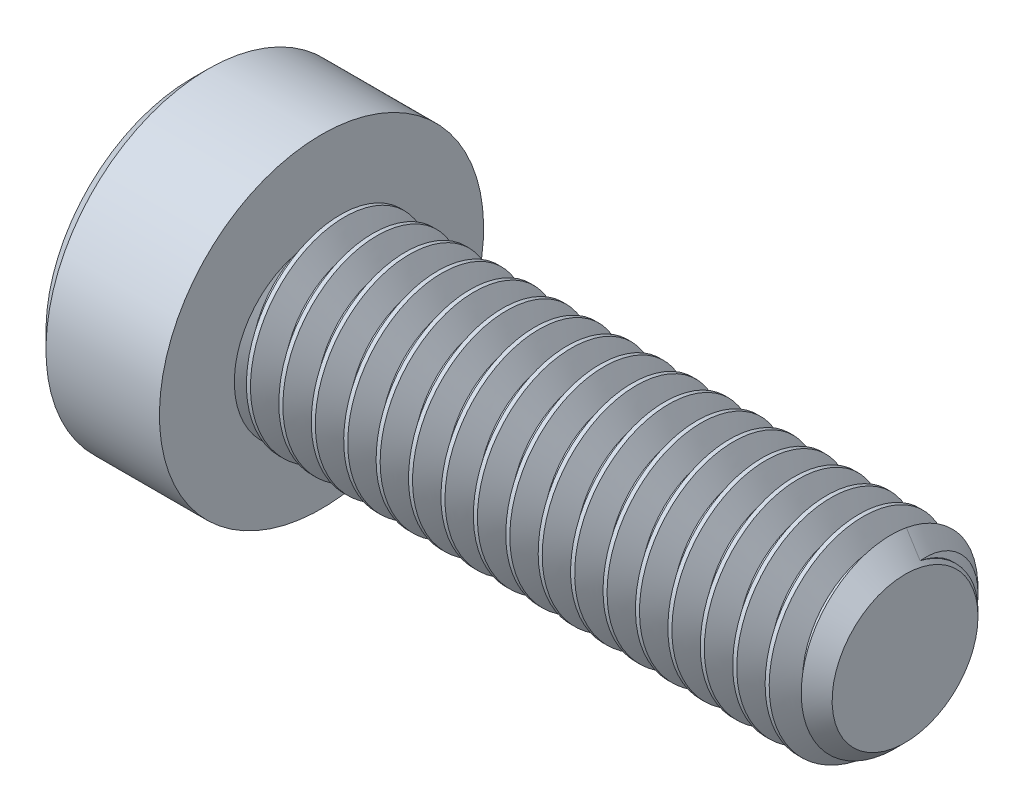
SolidWorks part; units mm, degrees
ref_plane "Front Plane" through (0, 0, 0) normal (0, 0, 1) x (1, 0, 0)
ref_plane "Top Plane" through (0, 0, 0) normal (0, 1, 0) x (1, 0, 0)
ref_plane "Right Plane" through (0, 0, 0) normal (1, 0, 0) x (0, 0, -1)
sketch "Sketch1" plane through (0, 0, 0) normal (0, 0, 1) x (1, 0, 0)
  line L0 (9, 0) -> (-9, 0) construction
  line L1 (9, 3) -> (9, -3) construction
  line L2 (-9, 5) -> (-9, -5) construction
  line L3 (-9, 5) -> (-12.5, 5) construction
  line L4 (-12.5, 5) -> (-13, 4.5) construction
  line L5 (-13, 4.5) -> (-13, -4.5) construction
  line L6 (-13, -4.5) -> (-12.5, -5) construction
  line L7 (-12.5, -5) -> (-9, -5) construction
  point P7 (-9.88, 0)
  point P12 (5, -3)
  dimension "D1" = 45
  dimension "Dec." = 6
  dimension "Length" = 18
  dimension "Head Dia" = 10
  dimension "Head Height" = 4
  dimension "Hex Depth" = 3.12
  dimension "Chamfer" = 0.5
  dimension "D2" = 4
ref_plane "Plane1" through (9, 0, 0) normal (1, 0, 0) x (0, 0, -1)
ref_plane "Plane2" through (-13, 0, 0) normal (1, 0, 0) x (0, 0, -1)
sketch "Sketch2" plane through (9, 0, 0) normal (1, 0, 0) x (0, 0, -1)
  circle A0 centre (0, 0) radius 3
extrude "Boss-Extrude1" add sketch "Sketch2" against normal up to vertex (18 mm away) up to point (-9, 0, 0)
sketch "Sketch3" plane through (9, 0, 0) normal (1, 0, 0) x (0, 0, -1)
  circle A0 centre (0, 0) radius 3 construction
  circle A1 centre (0, 0) radius 3
curve "Helix/Spiral1" pitch 1 height 19 radius 3 centre (9, 0, 0) axis (-1, 0, 0) start towards (0, 1, 0) parameters "Pitch"=1
chamfer "Chamfer1" distance 0.75 angle 45 1 edges at (9, 0, -3)
sketch "Sketch5" plane through (0, 0, 0) normal (0, 0, 1) x (1, 0, 0)
  line L0 (8.5625, 3) -> (9.4375, 3)
  line L1 (9.4375, 3) -> (9.0625, 2.3505)
  line L2 (9.0625, 2.3505) -> (8.9375, 2.3505)
  line L3 (8.9375, 2.3505) -> (8.5625, 3)
  line L4 (9, 2.3505) -> (9, 3) construction
  line L5 (8.75, 2.6752) -> (9.25, 2.6752) construction
  dimension "D1" = 60
  dimension "D2" = 0.5
  dimension "D3" = 0.125
sweep "Cut-Sweep1" cut profiles "Sketch5" path "Helix/Spiral1" align with end faces yes
sketch "Sketch4" plane through (-13, 0, 0) normal (1, 0, 0) x (0, 0, -1)
  line L0 (-5, 0.7937) -> (5, 0.7937) construction
  line L1 (0, 2.3094) -> (-2, 1.1547)
  line L2 (-2, 1.1547) -> (-2, -1.1547)
  line L3 (-2, -1.1547) -> (0, -2.3094)
  line L4 (0, -2.3094) -> (2, -1.1547)
  line L5 (2, -1.1547) -> (2, 1.1547)
  line L6 (2, 1.1547) -> (0, 2.3094)
  line L7 (0, 0) -> (0, 0.7937) construction
  circle A0 centre (0, 0) radius 2 construction
  dimension "Hex Size" = 4
  dimension "D1" = 10
  dimension "D2" = 0.7937
sketch "Sketch6" plane through (0, 0, 0) normal (0, 0, 1) x (1, 0, 0)
  line L0 (-12.5, 5) -> (-13, 4.5) construction
  line L1 (-9, 5) -> (-12.5, 5) construction
  line L2 (-9, 5) -> (-9, -5) construction
  line L3 (-13, 4.5) -> (-13, -4.5) construction
  line L4 (-12.5, 5) -> (-13, 4.5)
  line L5 (-9, 5) -> (-12.5, 5)
  line L6 (-9, 5) -> (-9, 0)
  line L7 (-13, 4.5) -> (-13, 0)
  line L8 (-9, 0) -> (-13, 0) construction
  line L9 (-9, 0) -> (-13, 0)
revolve "Revolve1" add sketch "Sketch6" angle 360 about L8
extrude "Cut-Extrude1" cut sketch "Sketch4" along normal up to vertex (3.12 mm away) up to point (-9.88, 0, 0)
sketch "Sketch8" plane through (-13, 0, 0) normal (-1, 0, 0) x (0, 0, 1)
  circle A1 centre (0, 0) radius 2.3094
extrude "Cut-Extrude2" cut sketch "Sketch8" against normal through all draft 45
equation "\"D3@Helix/Spiral1\" = \"Length@Sketch1\"+\"Pitch@Helix/Spiral1\""
equation "\"D3@Sketch5\" = \"Pitch@Helix/Spiral1\"*.125"
equation "\"D2@Sketch5\" = \"Pitch@Helix/Spiral1\"*.50"
equation "\"D1@Chamfer1\" = \"Pitch@Helix/Spiral1\"*.75"
equation "\"D2@Sketch1\" = \"Pitch@Helix/Spiral1\"*4"
equation "\"D1@Sketch4\" = \"Head Dia@Sketch1\""
equation "\"Chamfer@Sketch1\" = \"Head Height@Sketch1\"/8"
